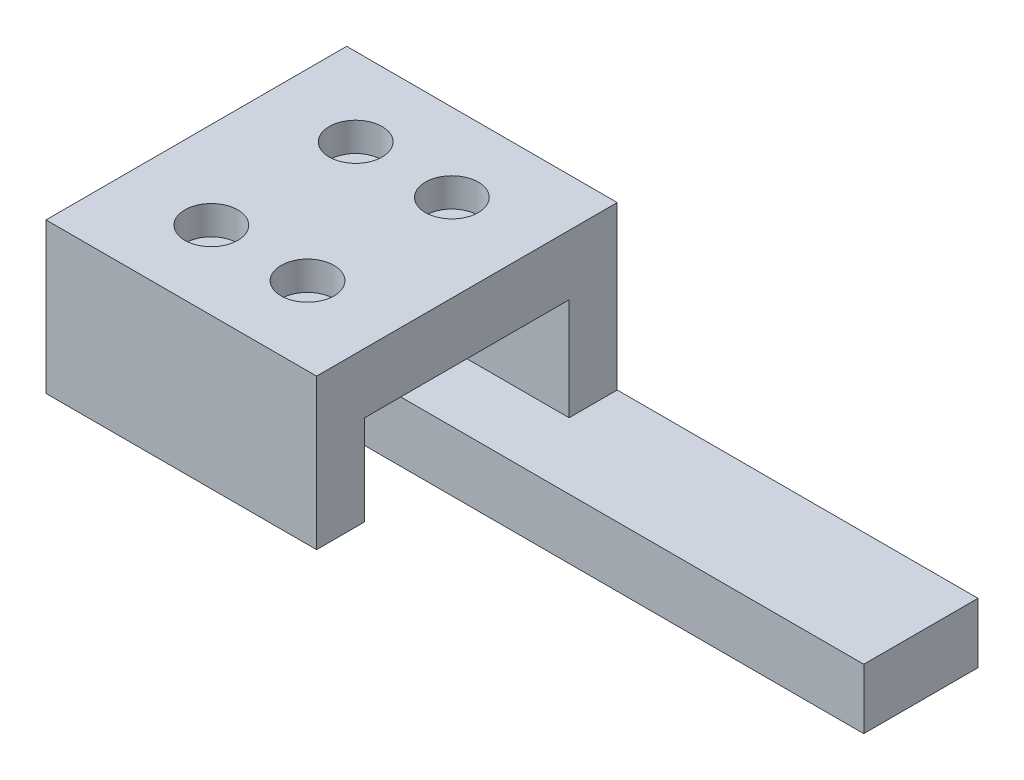
SolidWorks part; units mm, degrees
note: The reader was unsure of these and kept them because the rebuilt part matched: shared geometry of "Sketch1<3>", "Sketch1<4>".
ref_plane "Ebene vorne" through (0, 0, 0) normal (0, 0, 1) x (1, 0, 0)
ref_plane "Ebene oben" through (0, 0, 0) normal (0, 1, 0) x (1, 0, 0)
ref_plane "Ebene rechts" through (0, 0, 0) normal (1, 0, 0) x (0, 0, -1)
sketch "Sketch1" plane through (0, 0, 0) normal (0, 1, 0) x (1, 0, 0)
  line L1 (-11.25, -8.5) -> (11.25, -8.5)
  line L2 (-11.25, -8.5) -> (-11.25, 8.5)
  line L3 (-11.25, 8.5) -> (11.25, 8.5)
  line L4 (11.25, -8.5) -> (11.25, 8.5)
  line L5 (-11.25, -8.5) -> (11.25, 8.5) construction
  line L6 (-11.25, 8.5) -> (11.25, -8.5) construction
  line L7 (-11.25, -12.5) -> (11.25, -12.5)
  line L8 (-11.25, -12.5) -> (-11.25, 12.5)
  line L9 (-11.25, 12.5) -> (11.25, 12.5)
  line L10 (11.25, -12.5) -> (11.25, 12.5)
  line L11 (-11.25, -12.5) -> (11.25, 12.5) construction
  line L12 (-11.25, 12.5) -> (11.25, -12.5) construction
  point P0 (0, 0)
  point P5 (0, 0)
  dimension "D1" = 22.5
  dimension "D2" = 17
  dimension "D3" = 25
  dimension "D4" = 22.5
extrude "Boss-Extrude1" add sketch "Sketch1" along normal blind 5 contours L2 L1 L4 L3 | L8 L7 L10 L9
extrude "Boss-Extrude2" add sketch "Sketch1<3>" against normal blind 13.5 contours L3 L10 L9 L8
sketch "Sketch1<3>" plane through (0, 0, 0) normal (0, 1, 0) x (1, 0, 0) same geometry as "Sketch1"
hole_wizard "CBORE for M2 Hex Socket Head Cap Screw1" positions "Sketch3" profile "Sketch4" counterbore size "M2" standard "DIN"
sketch "Sketch3" plane through (0, 5, 0) normal (0, 1, 0) x (1, 0, 0)
  line L1 (-4, -6) -> (4, -6)
  line L2 (-4, -6) -> (-4, 6)
  line L3 (-4, 6) -> (4, 6)
  line L4 (4, -6) -> (4, 6)
  line L5 (-4, -6) -> (4, 6) construction
  line L6 (-4, 6) -> (4, -6) construction
  point P1 (0, 0)
  point P2 (4, 6)
  point P6 (-4, 6)
  point P7 (4, -6)
  point P42 (-4, -6)
  dimension "D1" = 12
  dimension "D2" = 8
sketch "Sketch4" plane through (-4, 5, 6) normal (1, 0, 0) x (0, 0, 1)
  line L0 (0, 0) -> (0, 18.5)
  line L1 (0, 18.5) -> (1.2, 18.5)
  line L3 (1.2, 18.5) -> (1.2, 2.4)
  line L4 (1.2, 2.4) -> (2.2, 2.4)
  line L5 (2.2, 2.4) -> (2.2, 0)
  line L7 (2.2, 0) -> (0, 0)
  line L11 (0, -6.35) -> (0, 107.95) construction
  dimension "Thru Hole Dia." = 2.4
  dimension "Thru Hole Depth" = 18.5
  dimension "C'Bore Dia." = 4.4
  dimension "C'Bore Depth" = 2.4
sketch "Sketch5" plane through (0, -13.5, 0) normal (0, -1, 0) x (1, 0, 0)
  line L0 (-11.25, -8.5) -> (-11.25, -3)
  line L1 (-11.25, -3) -> (41.25, -3)
  line L2 (41.25, -3) -> (41.25, -8.5)
  line L3 (41.25, -8.5) -> (11.25, -8.5)
  line L4 (11.25, -8.5) -> (11.25, -12.5) construction
  line L5 (11.25, -12.5) -> (41.25, -12.5)
  line L6 (11.25, -12.5) -> (11.25, -8.5)
  line L7 (11.25, -8.5) -> (41.25, -8.5)
  line L8 (41.25, -12.5) -> (41.25, -8.5)
  line L9 (11.25, -12.5) -> (41.25, -8.5) construction
  line L10 (11.25, -8.5) -> (41.25, -12.5) construction
  point P11 (26.25, -10.5)
  line M2 (11.25, -8.5) -> (-11.25, -8.5)
  line M4 (-11.25, -12.5) -> (11.25, -12.5)
  line M5 (11.25, -12.5) -> (11.25, -8.5)
  dimension "D1" = 5.5
  dimension "D2" = 30
extrude "Boss-Extrude3" add sketch "Sketch5" against normal offset from surface (5 mm away) 8.5 contours L2 L3 L0 L1 M5 M4 | L3 L2 L1 L0 M2
extrude "Boss-Extrude4" add sketch "Sketch1<4>" against normal offset from surface (7.5 mm away) 1 contours L7 L10 L1 L8 up to face at (13.75, -8.5, -8)
sketch "Sketch1<4>" plane through (0, 0, 0) normal (0, 1, 0) x (1, 0, 0) same geometry as "Sketch1"
